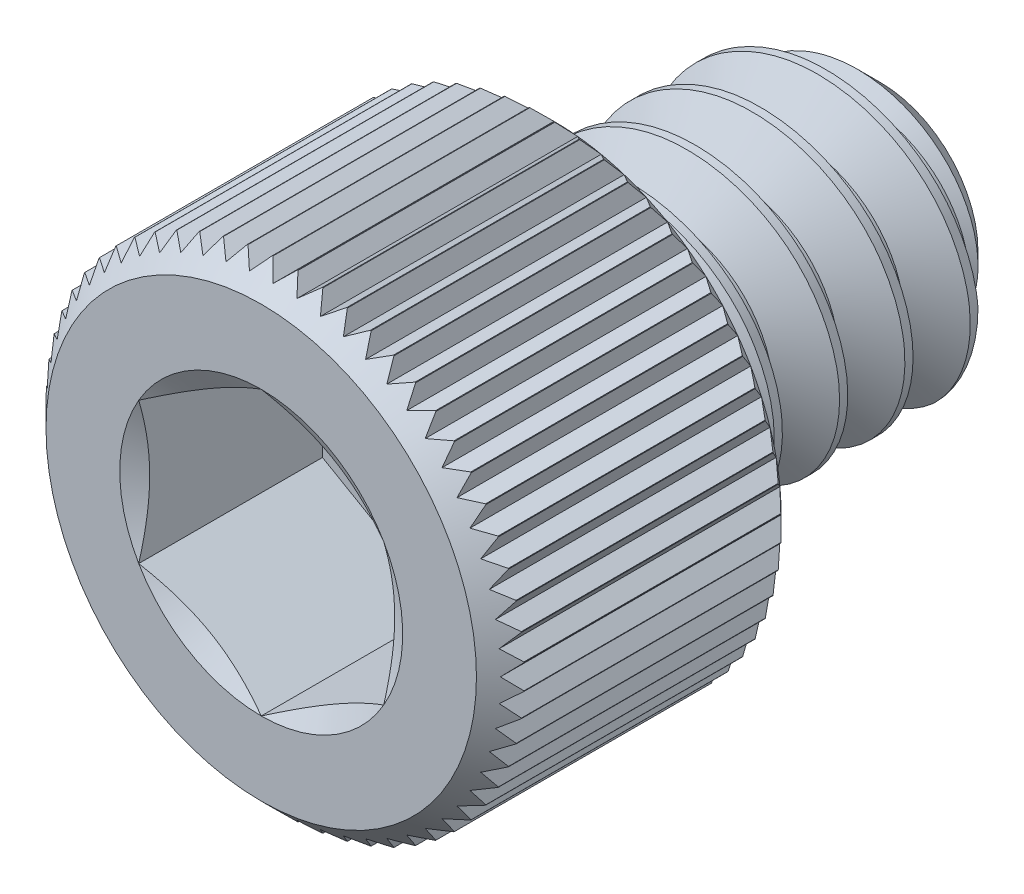
SolidWorks part; units mm, degrees
ref_plane "Front Plane" through (0, 0, 0) normal (0, 0, 1) x (1, 0, 0)
ref_plane "Top Plane" through (0, 0, 0) normal (0, 1, 0) x (1, 0, 0)
ref_plane "Right Plane" through (0, 0, 0) normal (1, 0, 0) x (0, 0, -1)
sketch "Sketch1" plane through (0, 0, 0) normal (1, 0, 0) x (0, 0, -1)
  line L0 (3.0099, 0) -> (-3.0099, 0) construction
  line L1 (-3.0099, 0) -> (-3.0099, 2.3241) construction
  line L2 (-0.1651, 1.4224) -> (-0.1651, 0) construction
  line L3 (2.3749, 0) -> (2.3749, 0.635) construction
  line L4 (-0.1651, 0) -> (-0.1651, -1.4224) construction
  point P6 (-3.0099, 1.1906)
  point P9 (-3.0099, -1.1906)
  point P10 (-0.1651, 0)
  point P13 (0.7874, -1.4224)
  dimension "Head Dia" = 4.6482
  dimension "Head Height" = 2.8448
  dimension "Thread OD" = 2.8448
  dimension "Pitch" = 0.635
  dimension "drive Size" = 2.3813
  dimension "D1" = 0.635
  dimension "D2" = 2.2225
sketch "Sketch2" plane through (0, 0, 0) normal (1, 0, 0) x (0, 0, -1)
  line L0 (3.0099, 0.9461) -> (2.5336, 1.4224)
  line L1 (-3.0099, 2.3241) -> (-0.1651, 2.3241)
  line L2 (-3.0099, 2.3241) -> (-3.0099, 0)
  line L4 (-0.1651, 2.3241) -> (-0.1651, 1.4224)
  line L5 (-0.1651, 1.4224) -> (2.5336, 1.4224)
  line L8 (3.0099, 0.9461) -> (3.0099, 0)
  line L9 (3.0099, 0) -> (-3.0099, 0) construction
  line L10 (3.0099, 0) -> (-3.0099, 0)
  dimension "D1" = 135
  dimension "D2" = 0.4763
revolve "Revolve1" add sketch "Sketch2" angle 360 about L10
sketch "Sketch4" plane through (0, 0, 3.0099) normal (0, 0, 1) x (1, 0, 0)
  line L1 (0, 1.3748) -> (-1.1906, 0.6874)
  line L2 (-1.1906, 0.6874) -> (-1.1906, -0.6874)
  line L3 (-1.1906, -0.6874) -> (0, -1.3748)
  line L4 (0, -1.3748) -> (1.1906, -0.6874)
  line L5 (1.1906, -0.6874) -> (1.1906, 0.6874)
  line L6 (1.1906, 0.6874) -> (0, 1.3748)
  circle A0 centre (0, 0) radius 1.1906 construction
  circle A1 centre (0, 0) radius 2.3241 construction
  circle A2 centre (0, 0) radius 2.3241 construction
  dimension "D1" = 2.3813
extrude "Cut-Extrude1" cut sketch "Sketch4" against normal blind 1.7859
sketch "Sketch5" plane through (0, 0, 3.0099) normal (0, 0, 1) x (1, 0, 0)
  circle A0 centre (0, 0) radius 1.3748
extrude "Cut-Extrude2" cut sketch "Sketch5" against normal blind 10 draft 60
chamfer "Chamfer1" distance 0.2324 angle 45 1 edges at (-2.3241, 0, 3.0099)
chamfer "Chamfer2" distance 0.1162 angle 45 1 edges at (-2.3241, 0, 0.1651)
sketch "Sketch3" plane through (0, 0, -3.0099) normal (0, 0, -1) x (-1, 0, 0)
  circle A0 centre (0, 0) radius 1.4224 construction
  circle A1 centre (0, 0) radius 1.4224
split "Split1" bodies to split 106 resulting bodies 114 115 split by face at (-2.2079, 0, 0.1651)
curve "Helix/Spiral1" pitch 0.635 height 3.81 radius 1.4224 centre (0, 0, -3.0099) axis (0, 0, 1) start towards (0, 1, 0)
sketch "Sketch7" plane through (0, 0, 0) normal (1, 0, 0) x (0, 0, -1)
  line L0 (2.9702, 1.4911) -> (3.2877, 0.9412) construction
  line L1 (3.2877, 0.9412) -> (3.6052, 1.4911) construction
  line L2 (3.6052, 1.4911) -> (2.9702, 1.4911) construction
  line L3 (3.0099, 1.4224) -> (3.5655, 1.4224)
  line L4 (3.2877, 1.4911) -> (3.2877, 1.4224) construction
  line L5 (3.2877, 1.4224) -> (3.2877, 1.01) construction
  line L6 (3.2877, 1.01) -> (3.2877, 0.9412) construction
  line L7 (3.248, 1.01) -> (3.3274, 1.01)
  line L8 (2.9901, 1.4568) -> (3.5854, 1.4568) construction
  line L9 (3.3274, 1.01) -> (3.5655, 1.4224)
  line L10 (3.248, 1.01) -> (3.0099, 1.4224)
  point P0 (3.2877, 1.4568)
  dimension "D1" = 0.635
  dimension "D2" = 0.0794
sweep "Cut-Sweep1" cut profiles "Sketch7" path "Helix/Spiral1" align with end faces yes
sketch "Sketch11" plane through (0, 0, 0.1651) normal (0, 0, -1) x (-1, 0, 0)
  circle A0 centre (0, 0) radius 1.4911
extrude "Boss-Extrude4" add sketch "Sketch11" along normal up to vertex (3.175 mm away) draft 45 up to point (0, 0, -3.0099)
sketch "Sketch9" plane through (0, 0, 0.1651) normal (0, 0, -1) x (-1, 0, 0)
  line L0 (0, 0) -> (0, 2.3241) construction
  line L1 (0, 2.2079) -> (-0.2436, 2.4403)
  line L2 (-0.2436, 2.4403) -> (0.2436, 2.4403)
  line L3 (0.2436, 2.4403) -> (0, 2.2079)
  line L4 (-0.1218, 2.3241) -> (0, 0) construction
  line L5 (0, 0) -> (0.1218, 2.3241) construction
  circle A0 centre (0, 0) radius 2.3241 construction
  circle A1 centre (0, 0) radius 2.2079 construction
  dimension "D1" = 0.2324
  dimension "D2" = 6
extrude "Cut-Extrude3" cut sketch "Sketch9" against normal up to next
pattern_circular "CirPattern1" count 60 over 360 about axis through (0, 0, 0.1651) along (0, 0, -1) of "Cut-Extrude3"
equation "\"D1@Sketch1\"=\"Pitch@Sketch1\""
equation "\"D2@Sketch2\"=\"D1@Sketch1\"*.75"
equation "\"D4@Helix/Spiral1\"=\"Pitch@Sketch1\""
equation "\"D3@Helix/Spiral1\"=\"Length@Sketch1\"+\"Pitch@Sketch1\""
equation "\"D1@Sketch4\"=\"drive Size@Sketch1\""
equation "\"D1@Cut-Extrude1\"=\"D1@Sketch4\"*.75"
equation "\"D19\"= \"D1@Sketch4\" * .75"
equation "\"D1@Chamfer1\" = \"Head Dia@Sketch1\" * .05"
equation "\"D1@Chamfer2\"=\"D1@Chamfer1\"/2"
equation "\"D2@Sketch7\"=\"D1@Sketch7\"/8"
equation "\"D1@Sketch7\"=\"D4@Helix/Spiral1\""
equation "\"D2@Sketch1\"=\"Pitch@Sketch1\"*3.5"
equation "\"D1@Sketch9\"=\"D1@Chamfer1\""
equation "\"D1@CirPattern1\"=\"D3@CirPattern1\"/\"D2@Sketch9\""
